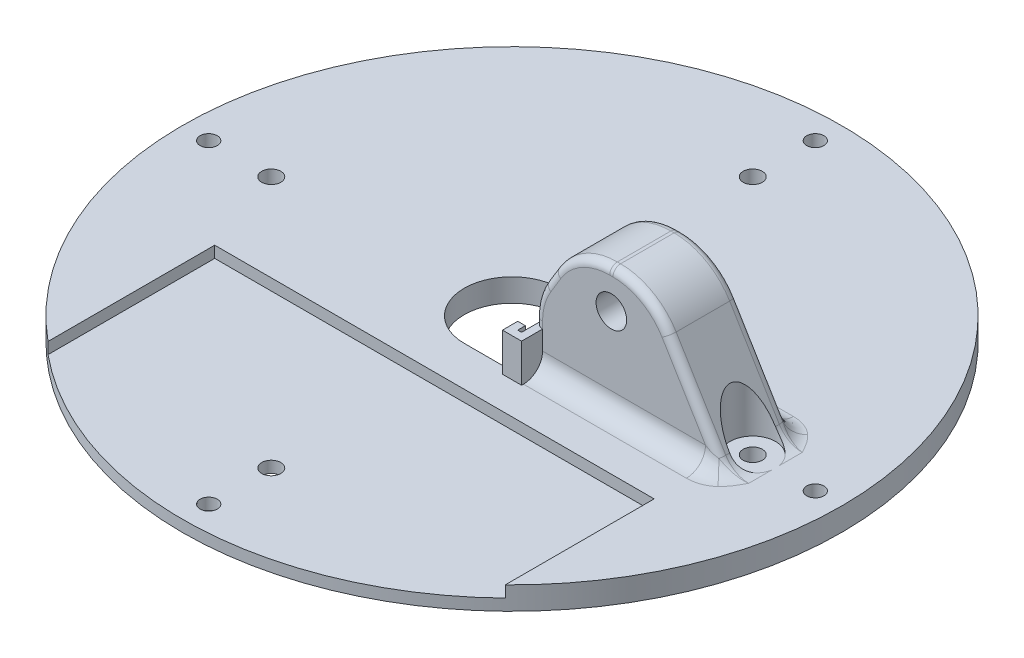
SolidWorks part; units mm, degrees
ref_plane "Front Plane" through (0, 0, 0) normal (0, 0, 1) x (1, 0, 0)
ref_plane "Top Plane" through (0, 0, 0) normal (0, 1, 0) x (1, 0, 0)
ref_plane "Right Plane" through (0, 0, 0) normal (1, 0, 0) x (0, 0, -1)
sketch "Sketch1" plane through (0, 0, 0) normal (0, 1, 0) x (1, 0, 0)
  circle A0 centre (0, 0) radius 86.25
  dimension "D1" = 172.5
extrude "Rotating Base" add sketch "Sketch1" along normal blind 6
sketch "Sketch2" plane through (0, 0, 0) normal (0, 1, 0) x (1, 0, 0)
  circle A0 centre (0, 63) radius 2.5
  circle A1 centre (63, 0) radius 2.5
  circle A2 centre (0, -63) radius 2.5
  circle A3 centre (-63, 0) radius 2.5
  point P12 (0, 0)
  dimension "D1" = 5
  dimension "D2" = 63
  dimension "D3" = 4
extrude "Internal Gear Mount" cut sketch "Sketch2" along normal blind 6
sketch "Sketch3" plane through (0, 0, 0) normal (0, 1, 0) x (1, 0, 0)
  circle A0 centre (0, 79.375) radius 2.25
  circle A1 centre (79.375, 0) radius 2.25
  circle A2 centre (0, -79.375) radius 2.25
  circle A3 centre (-79.375, 0) radius 2.25
  point P12 (0, 0)
  dimension "D1" = 79.375
  dimension "D2" = 4.5
  dimension "D3" = 4
extrude "Ring Bearing Mount" cut sketch "Sketch3" along normal blind 6
sketch "Sketch4" plane through (0, 0, 0) normal (0, 1, 0) x (1, 0, 0)
  line L0 (-3.3, 0) -> (3.3, 0) construction
  line L1 (25, 9) -> (45, 9)
  line L5 (25, 9) -> (25, -9)
  line L6 (45, -9) -> (45, 9)
  line L12 (25, -9) -> (45, -9)
  point P0 (35, 9)
  dimension "D1" = 20
  dimension "D2" = 18
  dimension "D3" = 35
extrude "Boss-Extrude1" add sketch "Sketch4" along normal blind 39
sketch "Sketch8" plane through (0, 0, 0) normal (0, 0, 1) x (1, 0, 0)
  line L1 (45, 6) -> (25, 6) construction
  circle A0 centre (35, 29) radius 2.5
  dimension "D2" = 5
  dimension "D3" = 23
  dimension "D1" = 35
extrude "Cut-Extrude4" cut sketch "Sketch8" against normal blind 10
sketch "Sketch9" plane through (0, 0, 0) normal (0, 0, 1) x (1, 0, 0)
  line L0 (86.25, 6) -> (-86.25, 6) construction
  circle A0 centre (35, 29) radius 4
  dimension "D1" = 8
  dimension "D2" = 23
  dimension "D3" = 35
extrude "Cut-Extrude5" cut sketch "Sketch9" along normal blind 10
sketch "Sketch10" plane through (0, 0, 0) normal (0, 0, 1) x (1, 0, 0)
  line L0 (25, 39) -> (5, 6)
  line L1 (25, 39) -> (25, 6) construction
  line L2 (86.25, 6) -> (-86.25, 6) construction
  line L3 (5, 6) -> (25, 6)
  line L4 (25, 6) -> (25, 39)
  line L5 (45, 39) -> (45, 6)
  line L6 (45, 39) -> (45, 6) construction
  line L7 (45, 6) -> (65, 6)
  line L8 (65, 6) -> (45, 39)
  dimension "D1" = 20
  dimension "D2" = 20
  dimension "D3" = 33
  dimension "D4" = 33
extrude "Boss-Extrude2" add sketch "Sketch10" along normal blind 9 and the other way blind 9
sketch "Sketch11" plane through (0, 6, 0) normal (0, 1, 0) x (1, 0, 0)
  circle A0 centre (63, 0) radius 6
  dimension "D1" = 12
extrude "Cut-Extrude6" cut sketch "Sketch11" along normal blind 15
sketch "Sketch7" plane through (0, 0, 0) normal (0, 1, 0) x (1, 0, 0)
  line L1 (0, 12.5) -> (15, 12.5)
  line L3 (0, -12.5) -> (15, -12.5)
  line L4 (15, 12.5) -> (15, -12.5)
  arc A0 (0, 12.5) -> (0, -12.5) centre (0, 0) ccw
  dimension "D1" = 25
  dimension "D2" = 15
extrude "Wiring Pass Through" cut sketch "Sketch7" along normal through all
fillet "Fillet1" radius 17 3 edges at (45, 39, 0) (25, 39, 0) (15, 22.5, 0)
fillet "Fillet2" radius 7 2 edges at (65, 6, 7.3284) (65, 6, -7.3284)
fillet "Fillet3" radius 2 16 edges at (65.5075, 6.901, -9) (56.4597, 20.0915, -9) (35, 39, -9) (65.5075, 6.901, 9) (56.4597, 20.0915, 9) (35, 39, 9) (18.7493, 28.6864, -9) (18.7493, 28.6864, 9) (43.7676, 36.812, -9) (26.2324, 36.812, -9) (43.7676, 36.812, 9) (26.2324, 36.812, 9) (15, 11.8753, -9) (15.627, 22.3248, -9) (15, 11.8753, 9) (15.627, 22.3248, 9)
ref_plane "Plane1" through (0, 3, 0) normal (0, 1, 0) x (1, 0, 0)
sketch "Sketch12" plane through (0, 3, 0) normal (0, 1, 0) x (1, 0, 0)
  line L0 (-54.9, -22.9) -> (-54.9, -66.5211)
  line L2 (-54.9, -22.9) -> (60.1, -22.9)
  line L3 (60.1, -22.9) -> (60.1, -61.8632)
  circle A0 centre (0, 0) radius 86.25 construction
  arc A1 (-54.9, -66.5211) -> (60.1, -61.8632) centre (0, 0) ccw
  dimension "D1" = 22.9
  dimension "D2" = 115
  dimension "D3" = 43.6211
extrude "Cut-Extrude7" cut sketch "Sketch12" along normal through all
fillet "Fillet4" radius 5 6 edges at (65.2409, 6, 8.6824) (65.2409, 6, -8.6824) (40.143, 6, 9) (40.143, 6, -9) (15.5858, 6, 8.4142) (15.5858, 6, -8.4142)
ref_plane "Plane2" through (0, 0, -20) normal (0, 0, 1) x (1, 0, 0)
ref_plane "Plane3" through (0, 16, 0) normal (0, 1, 0) x (1, 0, 0)
sketch "Sketch50" plane through (0, 16, 0) normal (0, 1, 0) x (1, 0, 0)
  line L0 (17, 14.5) -> (12, 14.5)
  line L2 (12, 14.5) -> (12, 10.5)
  line L3 (12, 10.5) -> (14, 10.5)
  line L4 (14, 10.5) -> (14, 12.5)
  line L5 (14, 12.5) -> (15, 12.5)
  line L6 (15, 12.5) -> (15, -12.5)
  line L9 (17, -14.5) -> (17, 14.5)
  line L11 (-21.45, 0) -> (21.45, 0) construction
  line L12 (14, -12.5) -> (15, -12.5)
  line L13 (14, -10.5) -> (14, -12.5)
  line L14 (12, -10.5) -> (14, -10.5)
  line L15 (12, -14.5) -> (12, -10.5)
  line L16 (17, -14.5) -> (12, -14.5)
  point P2 (17, 11.5)
  point P5 (0, 0)
  point P12 (0, 0)
  point P13 (0, 0)
  point P14 (0, 0)
  point P15 (0, 0)
  point P16 (0, 0)
  point P17 (0, 0)
  dimension "D1" = 2
  dimension "D2" = 1
  dimension "D3" = 5
  dimension "D4" = 14.5
  dimension "D5" = 15
  dimension "D7" = 2
  dimension "D8" = 4
extrude "Boss-Extrude3" add sketch "Sketch50" against normal up to surface (16 mm away) up to face at (0, 0, -77.125)
